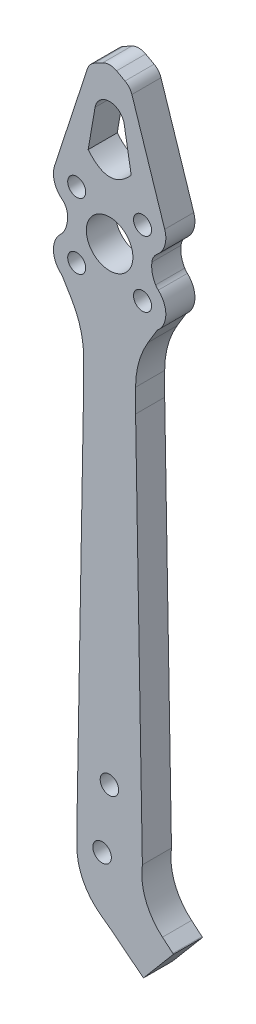
SolidWorks part; units mm, degrees
ref_plane "Alzado" through (0, 0, 0) normal (0, 0, 1) x (1, 0, 0)
ref_plane "Planta" through (0, 0, 0) normal (0, 1, 0) x (1, 0, 0)
ref_plane "Vista lateral" through (0, 0, 0) normal (1, 0, 0) x (0, 0, -1)
sketch "Croquis1" plane through (0, 0, 0) normal (0, 0, 1) x (1, 0, 0)
  line L0 (-3.6902, 12.1812) -> (-2.5021, 19.0797)
  line L5 (1.4432, 0) -> (-1.4432, 0) construction
  line L6 (0, 26.6547) -> (0, 27) construction
  line L7 (-9.4591, 6.8989) -> (-3.8261, 24.1432)
  line L8 (-2.6434, 25.5635) -> (-1.1937, 26.3513)
  line L9 (2.6434, 25.5635) -> (1.1937, 26.3513)
  line L10 (9.4591, 6.8989) -> (3.8261, 24.1432)
  line L11 (-4.4598, -19.1024) -> (-4.4598, -23.0928)
  line L12 (-6.609, -11.3656) -> (-8.1748, -8.7649)
  line L13 (0, 33.6082) -> (0, 9.9689)
  line L15 (6.609, -11.3656) -> (8.1748, -8.7649)
  line L16 (-4.4598, -23.0928) -> (-5.6262, -89.5928)
  line L19 (0.3787, -102.0361) -> (5.7125, -106.265)
  line L23 (0, 4) -> (2.2899, 4) construction
  line L25 (3.7077, 12.0797) -> (2.5021, 19.0797)
  line L26 (0, 0) -> (0, -84.7706) construction
  line L27 (4.4598, -23.0928) -> (5.6262, -89.5928)
  line L28 (4.4598, -19.1024) -> (4.4598, -23.0928)
  line L30 (10.8705, -100.1499) -> (9.0798, -98.6394)
  line L31 (-5.6262, -89.5928) -> (-5.6262, -92.5515)
  line L32 (-1.5765, -100.5886) -> (0.3787, -102.0361)
  line L33 (10.8705, -100.1499) -> (10.969, -100.2318)
  line L34 (10.969, -100.2318) -> (5.8106, -106.3478)
  line L35 (5.8106, -106.3478) -> (5.7125, -106.265)
  circle A0 centre (-5.6569, 5.6569) radius 1.55
  circle A1 centre (-5.6569, -5.6569) radius 1.55
  circle A2 centre (5.6569, -5.6569) radius 1.55
  circle A3 centre (5.6569, 5.6569) radius 1.55
  circle A5 centre (0, 0) radius 4
  arc A6 (8.1709, 2.5456) -> (9.4591, 6.8989) centre (5.6569, 5.6569) ccw
  arc A7 (-8.1709, 2.5456) -> (-9.4591, 6.8989) centre (-5.6569, 5.6569) cw
  arc A8 (8.3591, -2.7076) -> (8.1748, -8.7649) centre (5.6569, -5.6569) cw
  arc A9 (-8.3591, -2.7076) -> (-8.1748, -8.7649) centre (-5.6569, -5.6569) ccw
  arc A10 (-7.9055, -2.1526) -> (-7.2631, 0.9247) centre (-11.9961, 0.3069) ccw
  arc A11 (-6.6415, -4.4598) -> (-4.4598, -6.6415) centre (0, 0) ccw
  arc A12 (7.9055, -2.1526) -> (7.2631, 0.9247) centre (11.9961, 0.3069) cw
  arc A14 (4.4598, -6.6415) -> (6.6415, -4.4598) centre (0, 0) ccw
  arc A15 (6.6415, 4.4598) -> (4.4598, 6.6415) centre (0, 0) ccw
  arc A16 (-4.4598, 6.6415) -> (-6.6415, 4.4598) centre (0, 0) ccw
  arc A17 (8.1709, 2.5456) -> (7.2631, 0.9247) centre (9.7421, 0.6011) ccw
  arc A18 (7.9055, -2.1526) -> (8.3591, -2.7076) centre (10.048, -0.8644) ccw
  arc A19 (-7.9055, -2.1526) -> (-8.3591, -2.7076) centre (-10.048, -0.8644) cw
  arc A20 (-8.1709, 2.5456) -> (-7.2631, 0.9247) centre (-9.7421, 0.6011) cw
  arc A21 (2.6434, 25.5635) -> (3.8261, 24.1432) centre (1.4497, 23.3669) cw
  arc A22 (1.1937, 26.3513) -> (-1.1937, 26.3513) centre (0, 24.1547) ccw
  arc A23 (-2.6434, 25.5635) -> (-3.8261, 24.1432) centre (-1.4497, 23.3669) ccw
  arc A24 (-4.4598, -19.1024) -> (-6.609, -11.3656) centre (-19.4598, -19.1024) ccw
  arc A28 (2.5021, 19.0797) -> (-2.5021, 19.0797) centre (0, 18.6488) ccw
  arc A32 (4.4598, -19.1024) -> (6.609, -11.3656) centre (19.4598, -19.1024) cw
  arc A33 (9.0798, -98.6394) -> (5.6262, -89.5928) centre (15.5274, -90.9955) cw
  arc A36 (-5.6262, -92.5515) -> (-1.5765, -100.5886) centre (4.3738, -92.5515) ccw
  circle A41 centre (-1.2941, -91.1894) radius 1.59
  circle A42 centre (-0.0338, -80.5184) radius 1.5875
  spline S0 degree 2 poles (-3.6902, 12.1812) (-0.0399, 7.8077) (3.7077, 12.0797) knots 0 0 0 1 1 1
  point P16 (5.8117, -106.3464)
  point P46 (7.5969, 2.1588)
  point P49 (8.1666, -2.5422)
  point P52 (-8.1666, -2.5422)
  point P55 (-7.5969, 2.1588)
  point P58 (3.5173, 25.0886)
  point P64 (-3.5173, 25.0886)
  point P77 (4.2446, 10.2207)
  point P81 (-4.2446, 10.2207)
  dimension "D1" = 3.1
  dimension "D4" = 23
  dimension "D3" = 8
  dimension "D7" = 2.5
  dimension "D8" = 15
  dimension "D9" = 7
  dimension "D14" = 10
  dimension "D12" = 10
  dimension "D17" = 2.9587
  dimension "D2" = 16
  dimension "D5" = 11.3137
  dimension "D6" = 12
  dimension "D10" = 7
  dimension "D15" = 8
  dimension "D16" = 2.3427
  dimension "D20" = 66.5
extrude "Saliente-Extruir1" add sketch "Croquis1" along normal blind 5 contours L15 A8 A9 L12 A24 L11 L16 L32 L19 | L8 A23 L7 A7 A20 A10 A19 A9 A8 A18 A12 A17 A6 L10 A21 L9 A22 A3 A2 A0 A1 A5 region at (0.2588, -39.5273, 0)
sketch "Croquis2" plane through (0, 0, 5) normal (0, 0, 1) x (1, 0, 0)
  circle A0 centre (0, 0) radius 4
